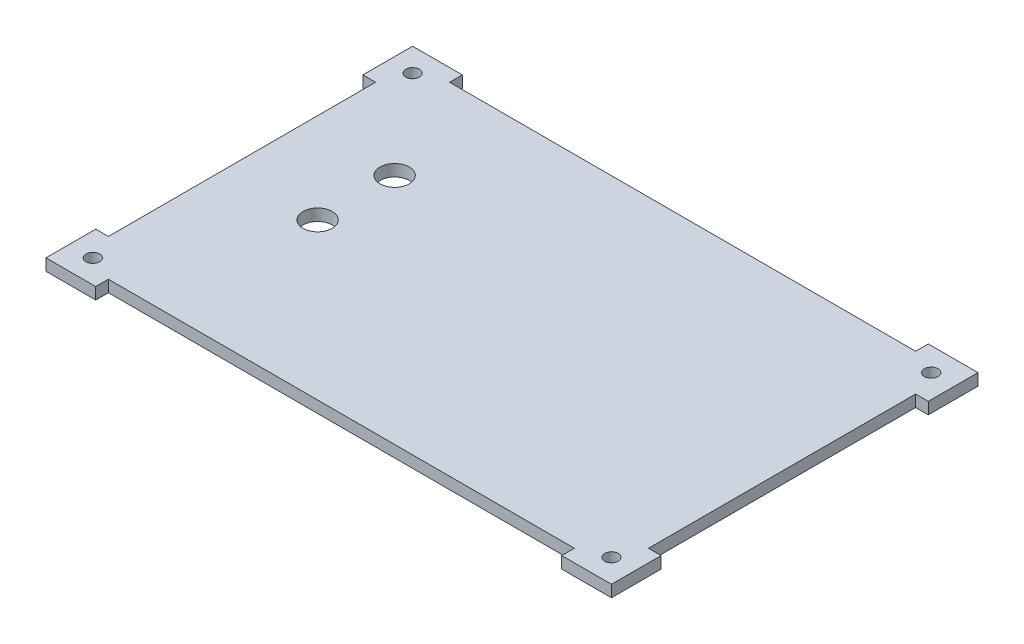
SolidWorks part; units mm, degrees
ref_plane "Front Plane" through (0, 0, 0) normal (0, 0, 1) x (1, 0, 0)
ref_plane "Top Plane" through (0, 0, 0) normal (0, 1, 0) x (1, 0, 0)
ref_plane "Right Plane" through (0, 0, 0) normal (1, 0, 0) x (0, 0, -1)
sketch "Sketch1" plane through (0, 0, 0) normal (0, 1, 0) x (1, 0, 0)
  line L1 (0, 0) -> (138.5, 0)
  line L2 (0, 0) -> (0, -87.5)
  line L3 (0, -87.5) -> (138.5, -87.5)
  line L4 (138.5, 0) -> (138.5, -87.5)
  dimension "D1" = 138.5
  dimension "D2" = 87.5
extrude "Boss-Extrude1" add sketch "Sketch1" along normal blind 3
sketch "Sketch2" plane through (0, 0, 0) normal (0, -1, 0) x (1, 0, 0)
  line L0 (0, 0) -> (0, 87.5) construction
  line L1 (0, 87.5) -> (138.5, 87.5) construction
  line L2 (138.5, 0) -> (0, 0) construction
  line L3 (138.5, 87.5) -> (138.5, 0) construction
  circle A0 centre (2.75, 84.75) radius 1.75
  circle A1 centre (135.75, 84.75) radius 1.75
  circle A2 centre (135.75, 2.75) radius 1.75
  circle A3 centre (2.75, 2.75) radius 1.75
  point P8 (2.75, 84.75)
  dimension "D1" = 3.5
  dimension "D2" = 2.75
  dimension "D3" = 2.75
  dimension "D4" = 2.75
  dimension "D5" = 2.75
  dimension "D6" = 2.75
  dimension "D7" = 2.75
  dimension "D8" = 2.75
  dimension "D9" = 2.75
extrude "Cut-Extrude1" cut sketch "Sketch2" against normal through all
sketch "Sketch3" plane through (0, 0, 0) normal (0, -1, 0) x (1, 0, 0)
  line L0 (0, 0) -> (0, 87.5) construction
  line L1 (-3.25, 90.75) -> (0, 90.75)
  line L2 (-3.25, 90.75) -> (-3.25, 78)
  line L3 (-3.25, 78) -> (0, 78)
  line L4 (0, 90.75) -> (0, 78)
  line L5 (0, 87.5) -> (138.5, 87.5) construction
  line L6 (0, 90.75) -> (9.5, 90.75)
  line L7 (0, 90.75) -> (0, 87.5)
  line L8 (0, 87.5) -> (9.5, 87.5)
  line L9 (9.5, 90.75) -> (9.5, 87.5)
  line L10 (138.5, 87.5) -> (138.5, 0) construction
  line L11 (138.5, 87.5) -> (129, 87.5)
  line L12 (138.5, 87.5) -> (138.5, 90.75)
  line L13 (138.5, 90.75) -> (129, 90.75)
  line L14 (129, 87.5) -> (129, 90.75)
  line L15 (138.5, 90.75) -> (141.75, 90.75)
  line L16 (138.5, 90.75) -> (138.5, 78)
  line L17 (138.5, 78) -> (141.75, 78)
  line L18 (141.75, 90.75) -> (141.75, 78)
  line L19 (138.5, 0) -> (0, 0) construction
  line L20 (0, 0) -> (-3.25, 0)
  line L21 (0, 0) -> (0, 9.5)
  line L22 (0, 9.5) -> (-3.25, 9.5)
  line L23 (-3.25, 0) -> (-3.25, 9.5)
  line L24 (-3.25, 0) -> (9.5, 0)
  line L25 (-3.25, 0) -> (-3.25, -3.25)
  line L26 (-3.25, -3.25) -> (9.5, -3.25)
  line L27 (9.5, 0) -> (9.5, -3.25)
  line L29 (138.5, 0) -> (141.75, 0)
  line L30 (138.5, 0) -> (138.5, 9.5)
  line L31 (138.5, 9.5) -> (141.75, 9.5)
  line L32 (141.75, 0) -> (141.75, 9.5)
  line L33 (141.75, 0) -> (129, 0)
  line L34 (141.75, 0) -> (141.75, -3.25)
  line L35 (141.75, -3.25) -> (129, -3.25)
  line L36 (129, 0) -> (129, -3.25)
  line M11 (0, 87.5) -> (0, 0)
  line M12 (0, 0) -> (138.5, 0)
  line M13 (138.5, 0) -> (138.5, 87.5)
  line M14 (138.5, 87.5) -> (0, 87.5)
  dimension "D1" = 9.5
  dimension "D2" = 9.5
  dimension "D3" = 3.25
  dimension "D4" = 3.25
  dimension "D5" = 3.25
  dimension "D6" = 3.25
  dimension "D7" = 9.5
  dimension "D8" = 9.5
  dimension "D9" = 3.25
  dimension "D10" = 3.25
  dimension "D11" = 9.5
  dimension "D12" = 9.5
  dimension "D13" = 3.25
  dimension "D14" = 3.25
  dimension "D15" = 9.5
  dimension "D16" = 9.5
extrude "Boss-Extrude2" add sketch "Sketch3" against normal through all contours L4 L1 L2 L3 M11 | L9 L6 L4 M14 | L23 L20 L22 M11 | L27 L20 L25 L26 M12 | L36 L35 L34 L29 M12 | L29 L32 L31 M13 | L14 L12 L13 M14 | L18 L15 L12 L17 M13 region at (-1.625, 0, 84.375) region at (4.75, 0, 89.125) region at (-1.625, 0, 4.75) region at (133.75, 0, 89.125) region at (3.125, 0, -1.625) region at (140.125, 0, 84.375) region at (135.375, 0, -1.625) region at (140.125, 0, 4.75)
sketch "Sketch4" plane through (0, 0, 0) normal (0, -1, 0) x (1, 0, 0)
  line L0 (0, 9.5) -> (0, 78) construction
  line L1 (9.5, 87.5) -> (129, 87.5) construction
  circle A0 centre (23.15, 47.5) radius 3.75
  circle A1 centre (23.15, 27.75) radius 3.75
  dimension "D1" = 7.5
  dimension "D2" = 7.5
  dimension "D3" = 23.15
  dimension "D4" = 40
  dimension "D5" = 23.15
  dimension "D6" = 19.75
extrude "Cut-Extrude2" cut sketch "Sketch4" against normal through all
equation "\"D4@Sketch2\"=\"D2@Sketch2\""
equation "\"D5@Sketch2\"=\"D4@Sketch2\""
equation "\"D6@Sketch2\"=\"D5@Sketch2\""
equation "\"D7@Sketch2\"=\"D6@Sketch2\""
equation "\"D8@Sketch2\"=\"D2@Sketch2\""
equation "\"D9@Sketch2\"=\"D8@Sketch2\""
equation "\"D2@Sketch4\"=\"D1@Sketch4\""
equation "\"D5@Sketch4\"=\"D3@Sketch4\""
